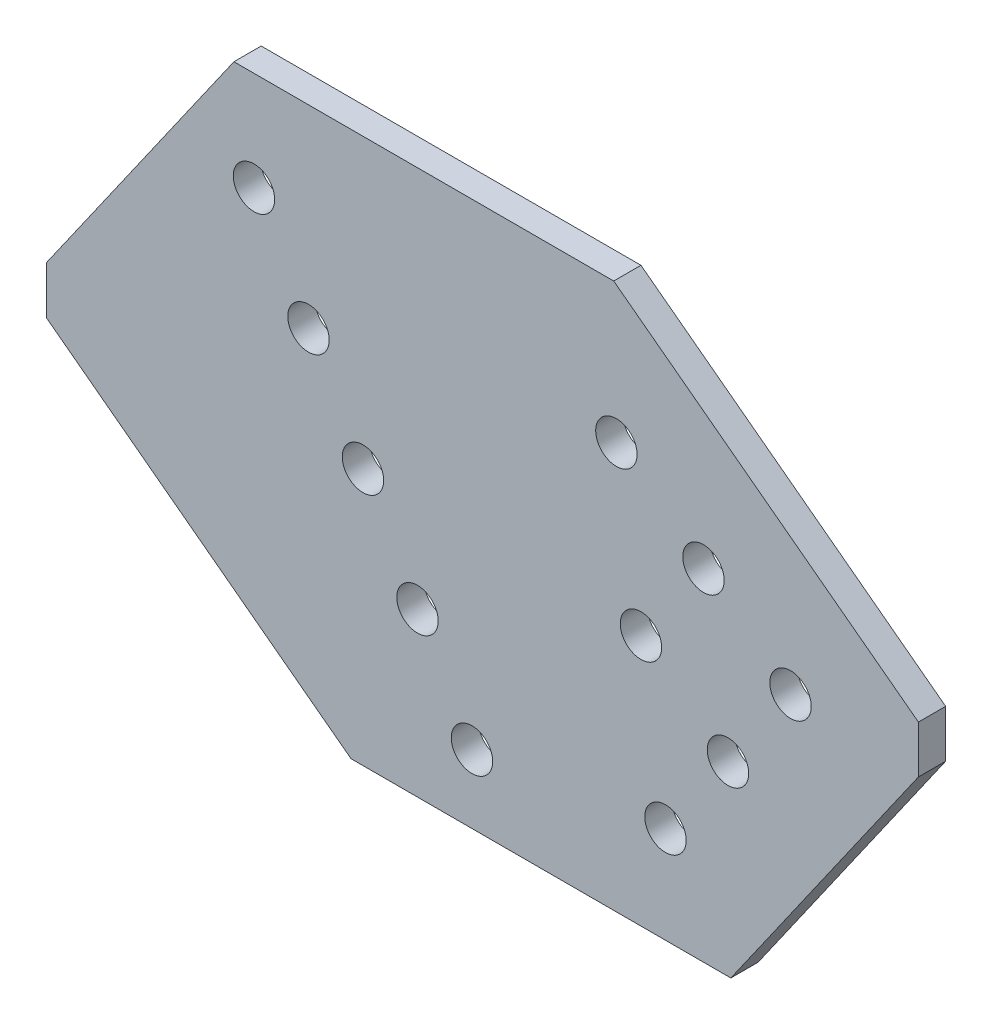
SolidWorks part; units mm, degrees
ref_plane "Front Plane" through (0, 0, 0) normal (0, 0, 1) x (1, 0, 0)
ref_plane "Top Plane" through (0, 0, 0) normal (0, 1, 0) x (1, 0, 0)
ref_plane "Right Plane" through (0, 0, 0) normal (1, 0, 0) x (0, 0, -1)
sketch "Sketch1" plane through (0, 0, 0) normal (0, 0, 1) x (1, 0, 0)
  line L1 (0, 0) -> (101.6, 0)
  line L2 (0, 0) -> (0, 63.5)
  line L3 (0, 63.5) -> (101.6, 63.5)
  line L4 (101.6, 0) -> (101.6, 63.5)
  dimension "D1" = 101.6
  dimension "D2" = 63.5
extrude "Boss-Extrude1" add sketch "Sketch1" along normal blind 3.175
sketch "Sketch2" plane through (0, 0, 3.175) normal (0, 0, 1) x (1, 0, 0)
  line L0 (101.6, 31.2097) -> (79.7467, 0)
  line L1 (101.6, 0) -> (101.6, 63.5) construction
  line L2 (0, 0) -> (101.6, 0) construction
  line L3 (101.6, 36.7493) -> (66.1007, 63.5)
  line L4 (101.6, 63.5) -> (0, 63.5) construction
  line L5 (66.1007, 63.5) -> (101.6, 63.5)
  line L6 (101.6, 63.5) -> (101.6, 36.7493)
  line L7 (101.6, 31.2097) -> (101.6, 0)
  line L8 (101.6, 0) -> (79.7467, 0)
  dimension "D1" = 55
  dimension "D2" = 37
  dimension "D3" = 38.1
  dimension "D4" = 44.45
extrude "Cut-Extrude1" cut sketch "Sketch2" against normal through all
sketch "Sketch3" plane through (0, 0, 3.175) normal (0, 0, 1) x (1, 0, 0)
  line L0 (21.8533, 63.5) -> (0, 32.2903)
  line L1 (66.1007, 63.5) -> (0, 63.5) construction
  line L2 (0, 63.5) -> (0, 0) construction
  line L3 (0, 32.2903) -> (0, 63.5)
  line L4 (0, 63.5) -> (21.8533, 63.5)
  line L5 (0, 0) -> (0, 26.7507)
  line L6 (0, 26.7507) -> (35.4993, 0)
  line L7 (0, 0) -> (79.7467, 0) construction
  line L8 (35.4993, 0) -> (0, 0)
  dimension "D1" = 55
  dimension "D2" = 38.1
  dimension "D3" = 44.45
  dimension "D4" = 37
extrude "Cut-Extrude2" cut sketch "Sketch3" against normal through all
sketch "Sketch4" plane through (0, 0, 3.175) normal (0, 0, 1) x (1, 0, 0)
  line L0 (26.7476, 47.5267) -> (55.9415, -3.0386) construction
  line L2 (35.4993, 0) -> (79.7467, 0) construction
  circle A0 centre (55.9415, -3.0386) radius 2.413 construction
  circle A1 centre (49.5915, 7.9599) radius 2.413
  circle A2 centre (43.2415, 18.9584) radius 2.413
  circle A3 centre (36.8915, 29.9569) radius 2.413
  circle A4 centre (30.5415, 40.9555) radius 2.413
  circle A5 centre (24.1915, 51.954) radius 2.413
  dimension "D2" = 4.826
  dimension "D1" = 60
  dimension "D3" = 6
extrude "Cut-Extrude3" cut sketch "Sketch4" against normal through all
sketch "Sketch5" plane through (0, 0, 3.175) normal (0, 0, 1) x (1, 0, 0)
  line L0 (101.6, 31.2097) -> (79.7467, 0) construction
  line L1 (66.1007, 63.5) -> (101.6, 36.7493) construction
  line L2 (86.7014, 32.0741) -> (71.9652, 11.0285) construction
  line L3 (86.7014, 32.0741) -> (55.3467, 55.7016) construction
  circle A0 centre (86.7014, 32.0741) radius 2.413
  circle A2 centre (76.5587, 39.7171) radius 2.413
  circle A3 centre (66.4161, 47.3602) radius 2.413
  circle A4 centre (56.2734, 55.0032) radius 2.413 construction
  circle A5 centre (69.2743, 29.3139) radius 2.413
  circle A6 centre (59.1317, 36.957) radius 2.413 construction
  circle A7 centre (48.989, 44.6) radius 2.413 construction
  circle A8 centre (61.9899, 18.9107) radius 2.413 construction
  circle A9 centre (51.8472, 26.5537) radius 2.413 construction
  circle A10 centre (41.7046, 34.1968) radius 2.413 construction
  circle A11 centre (79.417, 21.6709) radius 2.413
  circle A12 centre (72.1326, 11.2676) radius 2.413
  dimension "D1" = 4.826
  dimension "D2" = 12.7
  dimension "D3" = 12.7
  dimension "D4" = 4
  dimension "D5" = 3
extrude "Cut-Extrude4" cut sketch "Sketch5" against normal through all
